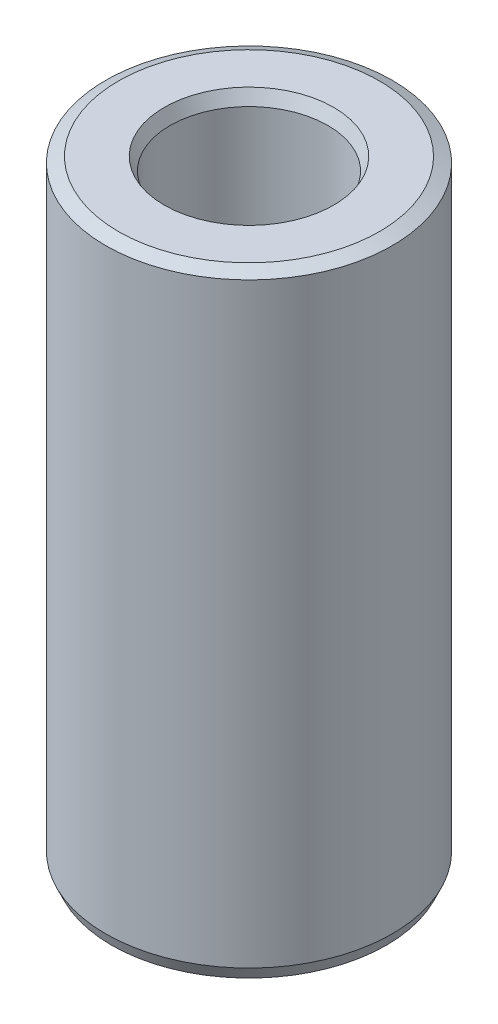
SolidWorks part; units mm, degrees
ref_plane "Front Plane" through (0, 0, 0) normal (0, 0, 1) x (1, 0, 0)
ref_plane "Top Plane" through (0, 0, 0) normal (0, 1, 0) x (1, 0, 0)
ref_plane "Right Plane" through (0, 0, 0) normal (1, 0, 0) x (0, 0, -1)
sketch "Sketch1" plane through (0, 0, 0) normal (0, 1, 0) x (1, 0, 0)
  circle A0 centre (0, 0) radius 32.5
  dimension "SLEEVE_OD" = 65
extrude "Boss-Extrude1" add sketch "Sketch1" along normal blind 139.3987
sketch "Sketch2" plane through (0, 0, 0) normal (0, 1, 0) x (1, 0, 0)
  circle A0 centre (0, 0) radius 17.9023
  dimension "BORE_D" = 35.8047
extrude "Cut-Extrude1" cut sketch "Sketch2" along normal through all
chamfer "Chamfer1" distance 1.3166 angle 65.572 4 edges at (0, 139.3987, 17.9023) (0, 0, 17.9023) (0, 0, 32.5) (0, 139.3987, 32.5) first distance on face at (0, 139.3987, 17.9023) first distance on face at (0, 0, 17.9023) first distance on face at (0, 139.3987, 32.5)
